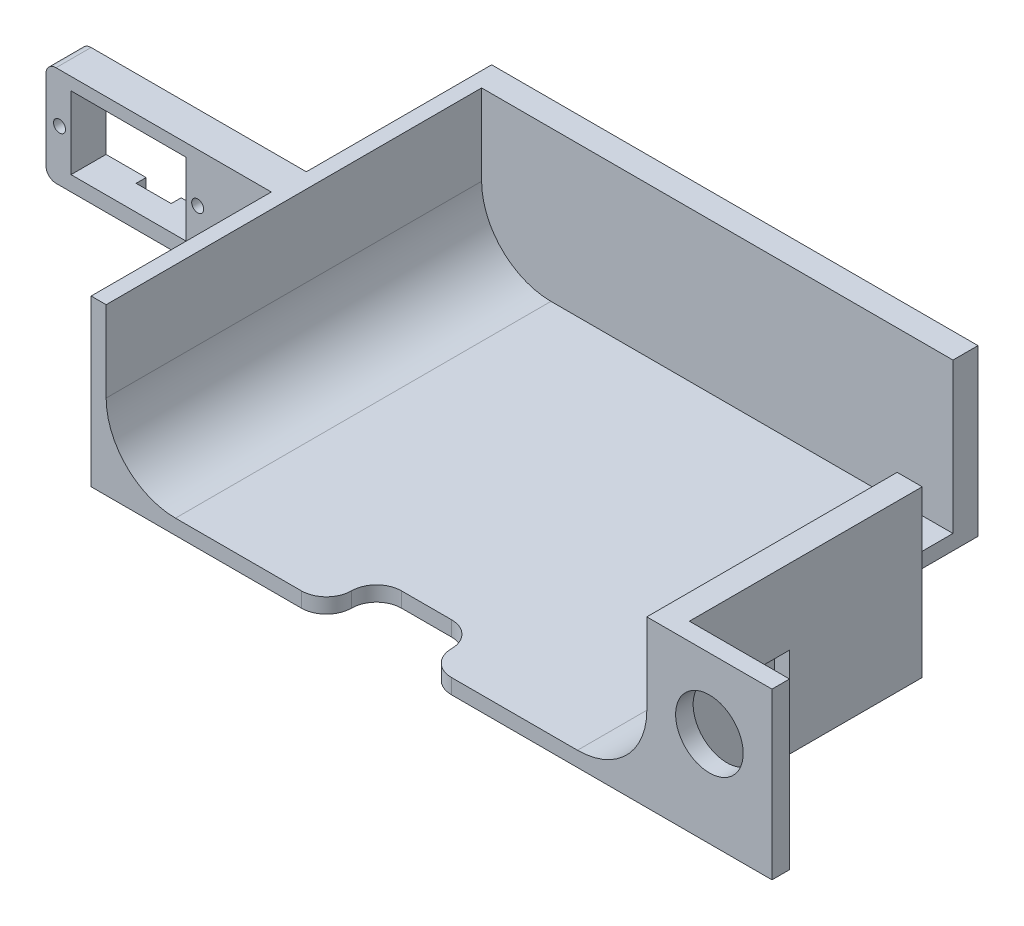
SolidWorks part; units mm, degrees
ref_plane "Plan de face" through (0, 0, 0) normal (0, 0, 1) x (1, 0, 0)
ref_plane "Plan de dessus" through (0, 0, 0) normal (0, 1, 0) x (1, 0, 0)
ref_plane "Plan de droite" through (0, 0, 0) normal (1, 0, 0) x (0, 0, -1)
sketch "Esquisse1" plane through (0, 0, 0) normal (0, 1, 0) x (1, 0, 0)
  line L1 (0, 0) -> (138, 0)
  line L2 (0, 0) -> (0, 75)
  line L3 (0, 75) -> (138, 75)
  line L4 (138, 0) -> (138, 75)
  dimension "D1" = 138
  dimension "D2" = 75
extrude "Boss.-Extru.1" add sketch "Esquisse1" along normal blind 3
sketch "Esquisse2" plane through (0, 3, 0) normal (0, 1, 0) x (1, 0, 0)
  line L0 (0, 0) -> (138, 0) construction
  line L1 (0, 75) -> (5, 75)
  line L2 (0, 75) -> (0, 0)
  line L3 (0, 0) -> (5, 0)
  line L4 (5, 75) -> (5, 0)
  line L6 (138, 75) -> (113, 75)
  line L7 (138, 75) -> (138, 0)
  line L8 (138, 0) -> (113, 0)
  line L9 (113, 75) -> (113, 0)
  dimension "D1" = 25
  dimension "D2" = 5
extrude "Boss.-Extru.2" add sketch "Esquisse2" along normal blind 30
fillet "Congé1" radius 13.85 2 edges at (113, 3, -37.5) (5, 3, -37.5)
sketch "Esquisse3" plane through (0, 0, -75) normal (0, 0, -1) x (-1, 0, 0)
  line L1 (-138, 0) -> (0, 0)
  line L2 (-138, 0) -> (-138, 33)
  line L3 (-138, 33) -> (0, 33)
  line L4 (0, 0) -> (0, 33)
extrude "Boss.-Extru.3" add sketch "Esquisse3" along normal blind 5
sketch "Esquisse4" plane through (0, 0, 0) normal (-1, 0, 0) x (0, 0, 1)
  line L1 (0, 33) -> (-25, 33)
  line L2 (0, 33) -> (0, 13)
  line L3 (0, 13) -> (-25, 13)
  line L4 (-25, 33) -> (-25, 13)
  dimension "D1" = 25
  dimension "D2" = 20
extrude "Enlèv. mat.-Extru.1" [suppressed] cut sketch "Esquisse4" against normal blind 6
sketch "Esquisse5" plane through (0, 33, 0) normal (0, 1, 0) x (1, 0, 0)
  line L0 (113, 75) -> (113, 0) construction
  line L1 (138, 80) -> (118, 80)
  line L2 (138, 80) -> (138, 3.5)
  line L3 (138, 3.5) -> (118, 3.5)
  line L4 (118, 80) -> (118, 3.5)
  line L5 (113, 0) -> (138, 0) construction
  dimension "D1" = 5
  dimension "D2" = 3.5
extrude "Enlèv. mat.-Extru.2" cut sketch "Esquisse5" against normal blind 30
sketch "Esquisse6" plane through (0, 0, 0) normal (0, 0, 1) x (1, 0, 0)
  line L0 (113, 33) -> (138, 33) construction
  line L3 (138, 33) -> (138, 0) construction
  circle A0 centre (125.5, 19) radius 6.25
  dimension "D3" = 12.5
  dimension "D1" = 14
  dimension "D2" = 12.5
extrude "Enlèv. mat.-Extru.3" cut sketch "Esquisse6" against normal up to surface (3.5 mm away) up to face at (128, 18, -3.5)
sketch "Esquisse7" plane through (0, 0, -80) normal (0, 0, -1) x (-1, 0, 0)
  line L1 (-138, 0) -> (-118, 0)
  line L2 (-138, 0) -> (-138, 3)
  line L3 (-138, 3) -> (-118, 3)
  line L4 (-118, 0) -> (-118, 3)
extrude "Enlèv. mat.-Extru.4" cut sketch "Esquisse7" against normal blind 30
sketch "Esquisse8" plane through (0, 33, 0) normal (0, 1, 0) x (1, 0, 0)
  line L0 (99.15, 0) -> (99.15, 75) construction
  line L1 (118, 80) -> (99.15, 80)
  line L2 (118, 80) -> (118, 50)
  line L3 (118, 50) -> (99.15, 50)
  line L4 (99.15, 80) -> (99.15, 50)
  dimension "D1" = 30
extrude "Enlèv. mat.-Extru.5" cut sketch "Esquisse8" against normal up to surface (33 mm away) up to face at (85.3333, 0, -43.3333)
sketch "Esquisse10" plane through (118, 0, 0) normal (1, 0, 0) x (0, 0, -1)
  line L0 (50, 3) -> (3.5, 3) construction
  line L1 (15.5, 3) -> (23.5, 3)
  line L2 (15.5, 3) -> (15.5, 18)
  line L3 (15.5, 18) -> (23.5, 18)
  line L4 (23.5, 3) -> (23.5, 18)
  dimension "D1" = 12
  dimension "D2" = 8
  dimension "D3" = 15
extrude "Enlèv. mat.-Extru.6" cut sketch "Esquisse10" against normal offset from surface (3 mm away) 2 up to face at (113, 24.925, -25)
sketch "Esquisse11" plane through (0, 3, 0) normal (0, 1, 0) x (1, 0, 0)
  line L1 (115, 23.5) -> (118, 23.5)
  line L2 (115, 23.5) -> (115, 15.5)
  line L3 (115, 15.5) -> (131, 15.5)
  line L8 (138, 3.5) -> (131, 3.5)
  line L9 (131, 15.5) -> (131, 3.5)
  line L10 (138, 50) -> (138, 3.5)
  line L11 (118, 50) -> (138, 50)
  line L12 (118, 50) -> (118, 23.5)
  dimension "D1" = 12
  dimension "D2" = 7
  dimension "D3" = 20
extrude "Enlèv. mat.-Extru.7" cut sketch "Esquisse11" against normal up to surface (3 mm away) up to face at (79.05, 0, -43.3333)
sketch "Esquisse12" plane through (0, 0, 0) normal (-1, 0, 0) x (0, 0, 1)
  line L1 (-80, 33) -> (0, 33)
  line L2 (-80, 33) -> (-80, 0)
  line L3 (-80, 0) -> (0, 0)
  line L4 (0, 33) -> (0, 0)
extrude "Enlèv. mat.-Extru.8" cut sketch "Esquisse12" against normal blind 2
sketch "Esquisse13" plane through (0, 0, 0) normal (0, 0, 1) x (1, 0, 0)
  line L0 (37, 0) -> (44.5969, -20)
  line L1 (2, 0) -> (138, 0) construction
  line L2 (44.5969, -20) -> (71.5969, -20)
  line L3 (71.5969, -20) -> (78, 0)
  line L4 (78, 0) -> (37, 0)
  line L7 (113, 33) -> (113, 16.85) construction
  dimension "D1" = 35
  dimension "D2" = 27
  dimension "D3" = 35
  dimension "D4" = 20
  dimension "D5" = 21
extrude "Boss.-Extru.4" [suppressed] add sketch "Esquisse13" against normal blind 7
sketch "Esquisse14" [suppressed] plane through (0, 0, 0) normal (0, 0, 1) x (1, 0, 0)
  line L0 (44.5969, -20) -> (71.5969, -20) construction
  line L1 (46.5, -2.5) -> (69.5, -2.5)
  line L2 (46.5, -2.5) -> (46.5, -17)
  line L3 (46.5, -17) -> (69.5, -17)
  line L4 (69.5, -2.5) -> (69.5, -17)
  dimension "D1" = 23
  dimension "D2" = 9.5
  dimension "D3" = 3
  dimension "D4" = 14.5
extrude "Enlèv. mat.-Extru.9" [suppressed] cut sketch "Esquisse14" against normal up to surface (7 mm away) up to face at (131.75, 19, 0)
fillet "Congé2" [suppressed] radius 10
sketch "Esquisse15" plane through (2, 0, 0) normal (-1, 0, 0) x (0, 0, 1)
  line L0 (0, 33) -> (-80, 33) construction
  line L1 (-42.9875, 33) -> (-35.9875, 33)
  line L2 (-42.9875, 33) -> (-42.9875, 13)
  line L3 (-42.9875, 13) -> (-35.9875, 13)
  line L4 (-35.9875, 33) -> (-35.9875, 13)
  dimension "D1" = 20
  dimension "D2" = 7
extrude "Boss.-Extru.5" add sketch "Esquisse15" along normal blind 45
sketch "Esquisse16" plane through (0, 0, -35.9875) normal (0, 0, 1) x (1, 0, 0)
  line L0 (-20.5, 33) -> (-20.5, 13) construction
  line L1 (-43, 33) -> (2, 33) construction
  line L2 (-43, 13) -> (2, 13) construction
  line L3 (-43, 23) -> (2, 23) construction
  line L4 (-43, 13) -> (-43, 33) construction
  line L5 (2, 13) -> (2, 33) construction
  line L7 (-38, 30.5) -> (-15, 30.5)
  line L8 (-38, 30.5) -> (-38, 16)
  line L9 (-38, 16) -> (-15, 16)
  line L10 (-15, 30.5) -> (-15, 16)
  dimension "D1" = 23
  dimension "D2" = 14.5
  dimension "D3" = 2.5
  dimension "D4" = 5
extrude "Enlèv. mat.-Extru.10" cut sketch "Esquisse16" against normal up to surface (7 mm away) up to face at (-20.5, 23, -42.9875)
fillet "Congé3" radius 20 1 edges at (2, 13, -39.4875)
fillet "Congé4" radius 2 2 edges at (-43, 33, -39.4875) (-43, 13, -39.4875)
sketch "Esquisse18" plane through (0, 0, -42.9875) normal (0, 0, -1) x (-1, 0, 0)
  line L0 (15, 16) -> (38, 16) construction
  line L1 (23, 16) -> (30, 16)
  line L2 (23, 16) -> (23, 13)
  line L3 (23, 13) -> (30, 13)
  line L4 (30, 16) -> (30, 13)
  line L6 (41, 13) -> (16.735, 13) construction
  dimension "D1" = 8
  dimension "D2" = 8
extrude "Enlèv. mat.-Extru.11" cut sketch "Esquisse18" against normal blind 2
sketch "Esquisse20" plane through (0, 0, -42.9875) normal (0, 0, -1) x (-1, 0, 0)
  line L0 (38, 30.5) -> (15, 30.5) construction
  line L1 (10.4, 25.9) -> (15, 25.9)
  line L2 (10.4, 25.9) -> (10.4, 20.6)
  line L3 (10.4, 20.6) -> (15, 20.6)
  line L4 (15, 25.9) -> (15, 20.6)
  line L5 (38, 25.9) -> (42.6, 25.9)
  line L6 (38, 25.9) -> (38, 20.6)
  line L7 (38, 20.6) -> (42.6, 20.6)
  line L8 (42.6, 25.9) -> (42.6, 20.6)
  line L9 (15, 16) -> (23, 16) construction
  line L10 (15, 30.5) -> (15, 16) construction
  line L11 (38, 16) -> (38, 30.5) construction
  line L12 (30, 16) -> (38, 16) construction
  dimension "D1" = 4.6
  dimension "D2" = 4.6
  dimension "D3" = 4.6
  dimension "D4" = 4.6
  dimension "D5" = 4.6
  dimension "D6" = 4.6
sketch "Esquisse21" plane through (0, 0, -42.9875) normal (0, 0, -1) x (-1, 0, 0)
  line L0 (15, 25.9) -> (15, 20.6) construction
  line L1 (10.4, 25.9) -> (10.4, 20.6) construction
  line L2 (10.4, 23.25) -> (15, 23.25) construction
  line L3 (15, 23.25) -> (42.6, 23.25) construction
  line L4 (42.6, 25.9) -> (42.6, 20.6) construction
  circle A0 centre (12.7, 23.25) radius 1
  circle A1 centre (40.3, 23.25) radius 1
  dimension "D1" = 2
  dimension "D3" = 2
  dimension "D2" = 2.3
extrude "Enlèv. mat.-Extru.12" cut sketch "Esquisse21" against normal up to surface (7 mm away) up to face at (-26.5, 23.25, -35.9875)
hole_wizard "Dégagement M21" positions "Esquisse22" profile "Esquisse23" hole size "M2" standard "ISO"
sketch "Esquisse22" plane through (0, 0, -42.9875) normal (0, 0, -1) x (-1, 0, 0)
  point P0 (40.3, 23.25)
  point P3 (12.7, 23.25)
sketch "Esquisse23" plane through (-40.3, 23.25, -42.9875) normal (1, 0, 0) x (0, 1, 0)
  line L0 (0, 0) -> (0, 10.721)
  line L1 (0, 10.721) -> (1.2, 10)
  line L2 (1.2, 10) -> (1.2, 0)
  line L5 (1.2, 0) -> (0, 0)
  line L10 (0, 10.721) -> (-1.2, 10) construction
  line L11 (0, -6.35) -> (0, 107.95) construction
  dimension "Diamètre du perçage" = 2.4
  dimension "Profondeur du perçage" = 10
  dimension "Angle de pointe" = 118
hole_wizard "Dégagement M121" positions "Esquisse24" profile "Esquisse25" hole size "M12" standard "ISO"
sketch "Esquisse24" plane through (0, 0, 0) normal (0, 0, 1) x (1, 0, 0)
  point P0 (125.5, 19)
sketch "Esquisse25" plane through (125.5, 19, 0) normal (1, 0, 0) x (0, -1, 0)
  line L0 (0, 0) -> (0, 14.0558)
  line L1 (0, 14.0558) -> (6.75, 10)
  line L2 (6.75, 10) -> (6.75, 0)
  line L5 (6.75, 0) -> (0, 0)
  line L10 (0, 14.0558) -> (-6.75, 10) construction
  line L11 (0, -6.35) -> (0, 107.95) construction
  dimension "Diamètre du perçage" = 13.5
  dimension "Profondeur du perçage" = 10
  dimension "Angle de pointe" = 118
sketch "Esquisse26" plane through (0, 0, 0) normal (0, 0, 1) x (1, 0, 0)
  line L0 (5, 33) -> (113, 33) construction
  line L1 (59, 33) -> (59, 0) construction
  line L2 (2, 0) -> (138, 0) construction
  line L3 (59, 3) -> (49, 3)
  line L4 (18.85, 3) -> (99.15, 3) construction
  line L5 (49, 3) -> (49, 0)
  line L6 (49, 0) -> (69, 0)
  line L7 (69, 0) -> (69, 3)
  line L8 (99.15, 3) -> (18.85, 3) construction
  line L9 (69, 3) -> (59, 3)
  dimension "D1" = 10
  dimension "D2" = 10
extrude "Enlèv. mat.-Extru.13" cut sketch "Esquisse26" against normal blind 10
fillet "Congé5" radius 5 4 edges at (69, 1.5, 0) (49, 1.5, 0) (49, 1.5, -10) (69, 1.5, -10)
sketch "Esquisse27" plane through (0, 0, 0) normal (0, -1, 0) x (1, 0, 0)
  line L0 (2, -80) -> (2, -42.9875) construction
  line L1 (2, -35.9875) -> (-8, -35.9875)
  line L2 (2, -35.9875) -> (2, -25.9875)
  line L3 (2, -25.9875) -> (-8, -25.9875)
  line L4 (-8, -35.9875) -> (-8, -25.9875)
  line L5 (2, -60) -> (-8, -60)
  line L6 (2, -60) -> (2, -70)
  line L7 (2, -70) -> (-8, -70)
  line L8 (-8, -60) -> (-8, -70)
  line L9 (99.15, -80) -> (2, -80) construction
  line L11 (12, -80) -> (22, -80)
  line L12 (12, -80) -> (12, -90)
  line L13 (12, -90) -> (22, -90)
  line L14 (22, -80) -> (22, -90)
  dimension "D1" = 10
  dimension "D2" = 10
  dimension "D3" = 10
  dimension "D4" = 10
  dimension "D5" = 10
  dimension "D6" = 10
  dimension "D7" = 10
  dimension "D8" = 10
extrude "Boss.-Extru.6" add sketch "Esquisse27" against normal blind 7
sketch "Esquisse28" plane through (0, 0, 0) normal (0, -1, 0) x (1, 0, 0)
  line L0 (118, -50) -> (99.15, -68.85)
  line L1 (99.15, -80) -> (99.15, -50) construction
  line L2 (99.15, -68.85) -> (99.15, -50)
  line L3 (99.15, -50) -> (118, -50)
  dimension "D1" = 18.85
extrude "Boss.-Extru.7" add sketch "Esquisse28" against normal blind 3
sketch "Esquisse31" plane through (0, 0, 0) normal (0, -1, 0) x (1, 0, 0)
  line L0 (2, -25.9875) -> (-8, -25.9875) construction
  line L1 (2, -25.9875) -> (2, 0) construction
  line L2 (2, -60) -> (-8, -60) construction
  line L6 (-8, -60) -> (-8, -70) construction
  line L7 (22, -90) -> (22, -80) construction
  line L8 (12, -90) -> (22, -90) construction
  line L9 (118, -50) -> (118, -23.5) construction
  circle A0 centre (-3, -30.9875) radius 1.5
  circle A1 centre (-3, -65) radius 1.5
  circle A2 centre (17, -85) radius 1.5
  circle A3 centre (104, -54.85) radius 1.5
  point P14 (0, 0)
  point P16 (-8, -68.3656)
  point P17 (-8, -67.4849)
  point P18 (-8, -61.2646)
  dimension "D3" = 3
  dimension "D6" = 3
  dimension "D8" = 3
  dimension "D11" = 3
  dimension "D1" = 5
  dimension "D2" = 5
  dimension "D4" = 5
  dimension "D5" = 5
  dimension "D7" = 5
  dimension "D9" = 5
  dimension "D10" = 14
  dimension "D12" = 14
extrude "Enlèv. mat.-Extru.14" cut sketch "Esquisse31" against normal blind 7
hole_wizard "Fraisage pour vis à tête fraisée M31" positions "Esquisse32" profile "Esquisse33" countersink size "M3" standard "ISO"
sketch "Esquisse32" plane through (0, 3, 0) normal (0, 1, 0) x (1, 0, 0)
  point P0 (104, 54.85)
sketch "Esquisse33" plane through (104, 3, -54.85) normal (1, 0, 0) x (0, 0, 1)
  line L0 (0, 0) -> (0, 11.0215)
  line L1 (0, 11.0215) -> (1.7, 10)
  line L2 (1.7, 10) -> (1.7, 1.45)
  line L3 (1.7, 1.45) -> (3.15, 0)
  line L5 (3.15, 0) -> (0, 0)
  line L6 (-1.7, 1.45) -> (-3.15, 0) construction
  line L10 (0, 11.0215) -> (-1.7, 10) construction
  line L11 (0, -6.35) -> (0, 107.95) construction
  dimension "Diamètre du perçage" = 3.4
  dimension "Profondeur du perçage" = 10
  dimension "Diamètre du fraisage entrant" = 6.3
  dimension "Angle du fraisage entrant" = 90
  dimension "Angle de pointe" = 118
hole_wizard "Fraisage pour vis à tête fraisée M32" positions "Esquisse34" profile "Esquisse35" countersink size "M3" standard "ISO"
sketch "Esquisse34" plane through (0, 7, 0) normal (0, 1, 0) x (1, 0, 0)
  point P0 (-3, 30.9875)
  point P3 (-3, 65)
  point P6 (17, 85)
sketch "Esquisse35" plane through (-3, 7, -30.9875) normal (1, 0, 0) x (0, 0, 1)
  line L0 (0, 0) -> (0, 11.0215)
  line L1 (0, 11.0215) -> (1.7, 10)
  line L2 (1.7, 10) -> (1.7, 1.45)
  line L3 (1.7, 1.45) -> (3.15, 0)
  line L5 (3.15, 0) -> (0, 0)
  line L6 (-1.7, 1.45) -> (-3.15, 0) construction
  line L10 (0, 11.0215) -> (-1.7, 10) construction
  line L11 (0, -6.35) -> (0, 107.95) construction
  dimension "Diamètre du perçage" = 3.4
  dimension "Profondeur du perçage" = 10
  dimension "Diamètre du fraisage entrant" = 6.3
  dimension "Angle du fraisage entrant" = 90
  dimension "Angle de pointe" = 118
sketch "Esquisse36" plane through (0, 3, 0) normal (0, 1, 0) x (1, 0, 0)
  line L1 (131, 15.5) -> (118, 15.5)
  line L2 (131, 15.5) -> (131, 3.5)
  line L3 (131, 3.5) -> (118, 3.5)
  line L4 (118, 15.5) -> (118, 3.5)
extrude "Enlèv. mat.-Extru.15" cut sketch "Esquisse36" against normal up to surface (3 mm away) up to face at (-3, 0, -32.6875)
